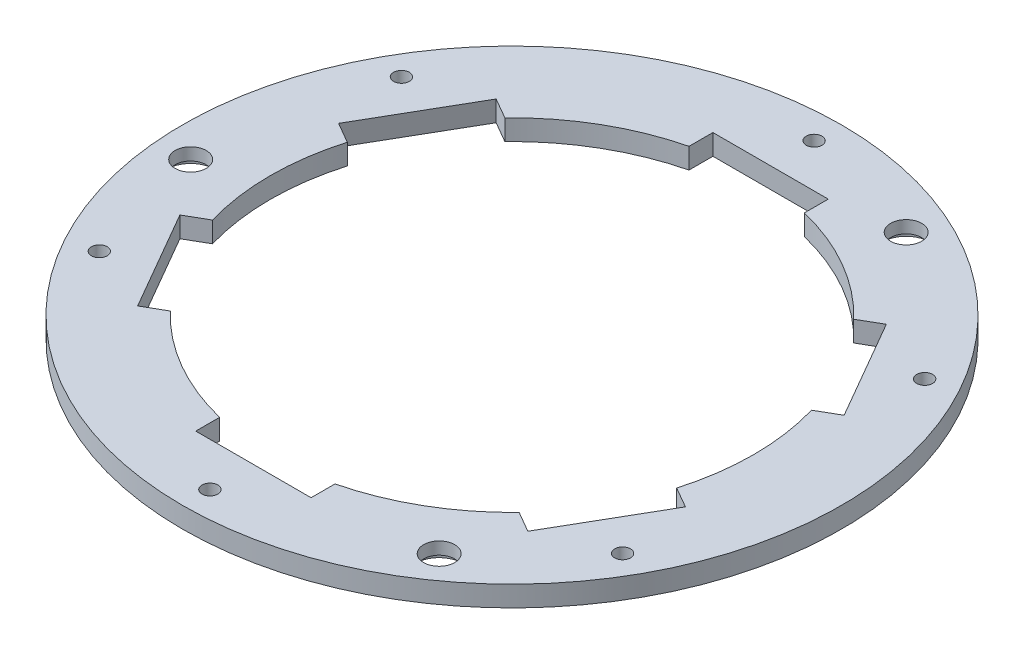
SolidWorks part; units mm, degrees
material "6061 Alloy"
ref_plane "Front Plane" through (0, 0, 0) normal (0, 0, 1) x (1, 0, 0)
ref_plane "Top Plane" through (0, 0, 0) normal (0, 1, 0) x (1, 0, 0)
ref_plane "Right Plane" through (0, 0, 0) normal (1, 0, 0) x (0, 0, -1)
sketch "Sketch1" plane through (0, 0, 0) normal (0, 1, 0) x (1, 0, 0)
  line L0 (-13.335, -54.2656) -> (-13.335, -58.1814)
  line L1 (13.335, -54.2656) -> (13.335, -58.1814)
  line L2 (-13.335, -59.7901) -> (13.335, -59.7901)
  line L3 (13.335, -58.1814) -> (13.335, -59.7901)
  line L4 (-13.335, -58.1814) -> (-13.335, -59.7901)
  line L5 (0, 0) -> (-68.319, -5.9771) construction
  line L6 (0, 0) -> (0, -23.1086) construction
  line L7 (0, 0) -> (17.8146, -65.9496) construction
  line L8 (0, 0) -> (27.4515, -55.5868) construction
  circle A0 centre (0, 0) radius 55.88
  circle A1 centre (0, 0) radius 76.2
  circle A2 centre (0, 0) radius 59.69
  circle A3 centre (0, -69.85) radius 1.8288
  circle A4 centre (-68.319, -5.9771) radius 3.5941
  dimension "D1" = 111.76
  dimension "D2" = 152.4
  dimension "D8" = 3.6576
  dimension "D11" = 7.1882
  dimension "D4" = 13.335
  dimension "D5" = 13.335
  dimension "D7" = 69.85
  dimension "D6" = 5.5245
  dimension "D9" = 68.58
  dimension "D10" = 85
  dimension "D13" = 17.8146
  dimension "D14" = 68.3133
  dimension "D16" = 61.9958
  dimension "D17" = 14.1512
  dimension "D3" = 3.81
extrude "Boss-Extrude1" add sketch "Sketch1" along normal blind 4.7625 contours L1 A2 L0 A0 | A1 A2 A0 region at (-15.0127, 0, 56.2235) region at (-74.0447, 0, 0)
pattern_circular "CirPattern1" count 6 over 360 about axis through (0, 4.7625, 0) along (0, 1, 0) of face at (-13.335, 2.3813, 57.0278) of face at (13.335, 2.3813, 57.0278) of face at (0, 4.7625, 71.6788) of face at (0, 2.3813, 59.7901)
sketch "Sketch2" plane through (0, 0, 0) normal (1, 0, 0) x (0, 0, -1)
  line L0 (76.2, 4.7625) -> (-76.2, 4.7625) construction
  line L1 (-76.2, 0) -> (76.2, 0) construction
  line L2 (76.2, 4.7625) -> (-76.2, 4.7625)
  line L3 (-76.2, 0) -> (76.2, 0)
  line L4 (0, 0) -> (0, 4.7625) construction
  circle A0 centre (-75.2856, 0) radius 2.667
  dimension "D1" = 5.334
  dimension "D2" = 0.9144
revolve "Cut-Revolve1" [suppressed] cut sketch "Sketch2" angle 360 about L4
sketch "Sketch4" plane through (0, 0, 0) normal (0, -1, 0) x (1, 0, 0)
  line L0 (0, 0) -> (-68.319, 5.9771) construction
  line L1 (0, 0) -> (0, -39.7137) construction
  circle A0 centre (-68.319, 5.9771) radius 5.588
  circle A2 centre (-68.319, 5.9771) radius 3.5941 construction
  circle A3 centre (-68.319, 5.9771) radius 3.5941
  dimension "D2" = 11.176
extrude "Cut-Extrude1" cut sketch "Sketch4" against normal blind 1.905 contours A0 region at (-73.749, 0, 5.9771)
pattern_circular "CirPattern2" count 3 over 360 about axis through (0, 0, 0) along (0, 1, 0) of face at (-68.319, 4.7625, 9.5712) of face at (-68.319, 1.905, 2.383) of face at (-68.319, 1.905, 0.3891)
sketch "Sketch5" plane through (0, 4.7625, 0) normal (0, 1, 0) x (1, 0, 0)
  line L0 (0, 0) -> (-20.0894, -55.1952)
  line L1 (0, 0) -> (0, -18.6852)
  line L2 (-16.5968, -53.0258) -> (-18.2257, -57.5011) construction
  line L3 (-18.2257, -57.5011) -> (-22.9993, -55.7636) construction
  line L4 (-22.9993, -55.7636) -> (-21.3704, -51.2884) construction
  line L5 (-59.7924, -7.9638) -> (-55.1022, -7.1368)
  line L6 (-54.2201, -12.1397) -> (-58.9103, -12.9667)
  line L7 (-58.9103, -12.9667) -> (-59.7924, -7.9638)
  line L8 (-36.7931, 47.7998) -> (-33.7318, 44.1515)
  line L9 (-37.6233, 40.8862) -> (-40.6846, 44.5345)
  line L10 (-40.6846, 44.5345) -> (-36.7931, 47.7998)
  line L11 (22.9993, 55.7636) -> (21.3704, 51.2884)
  line L12 (16.5968, 53.0258) -> (18.2257, 57.5011)
  line L13 (18.2257, 57.5011) -> (22.9993, 55.7636)
  line L14 (59.7924, 7.9638) -> (55.1022, 7.1368)
  line L15 (54.2201, 12.1397) -> (58.9103, 12.9667)
  line L16 (58.9103, 12.9667) -> (59.7924, 7.9638)
  line L17 (36.7931, -47.7998) -> (33.7318, -44.1515)
  line L18 (37.6233, -40.8862) -> (40.6846, -44.5345)
  line L19 (40.6846, -44.5345) -> (36.7931, -47.7998)
  circle A0 centre (0, 0) radius 55.5625
  circle A1 centre (0, 0) radius 58.7375 construction
  circle A2 centre (0, 0) radius 55.5625
  circle A3 centre (0, 0) radius 55.5625
  circle A4 centre (0, 0) radius 55.5625
  circle A5 centre (0, 0) radius 55.5625
  circle A6 centre (0, 0) radius 55.5625
  circle A7 centre (0, 0) radius 76.2
  circle A8 centre (0, 0) radius 63.5
  point P38 (0, 0)
  dimension "D1" = 111.125
  dimension "D3" = 20
  dimension "D4" = 2.54
  dimension "D5" = 4.7625
  dimension "D6" = 2.54
  dimension "D2" = 3.175
  dimension "D8" = 12.7
  dimension "D7" = 6
split line "Split Line1" [suppressed]
equation "\"Middle Coupler Inner Daimeter\"= 3.875in"
equation "\"Middle Coupler  Wall Thickness\" = 0.25in"
equation "\"Middle Coupler Bottom Thickness\"= 0.2in"
equation "\"Bearing Rail Offset\"= 0.45in"
equation "\"3-56 UNF Tap\"= 0.089in"
equation "\"3-56 UNF Clearance\"= 0.104in"
equation "\"Ball Bearing Distance\"= 0.03in"
equation "\"D1@Sketch1\"=\"Middle Coupler Inner Daimeter\"+0.5+0.0125*2in"
equation "\"TCA Outer Diameter\" = 6in"
equation "\"D2@Sketch1\"=\"TCA Outer Diameter\""
equation "\"D4@Sketch1\"=0.50 + (0.05/2)"
equation "\"D5@Sketch1\"=\"D4@Sketch1\""
equation "\"D7@Sketch1\"=(\"D2@Sketch1\"-0.5)/2"
equation "\"D8@Sketch1\"=\"6-32 Clearance\""
equation "\"D2@Sketch2\"=\"Interstage Aeroframe Wall Thickness\"/2"
equation "\"Interstage Aeroframe Wall Thickness\" = 0.072in"
equation "\"Compression Spring OD\"= 0.42in"
equation "\"10-24 Tap\"= 0.157in"
equation "\"10-24 Clearance\"= 0.196in"
equation "\"D2@Sketch4\"=\"Compression Spring OD\"+0.02"
equation "\"D3@Sketch1\"=0.125in+(0.05/2)"
equation "\"Lower Stage Fuselage Wall Thickness\" = 0.25in"
equation "\"6-32 Tap\" = 0.107in"
equation "\"1/4-20 Tap\" = 0.201in"
equation "\"3-48 Tap\"= 0.079in"
equation "\"12-24 Tap\" = 0.177in"
equation "\"3-48 Clearance\" = 0.104in"
equation "\"6-32 Clearance\" = 0.144"
equation "\"D6@Sketch1\"=3/16 + 0.03"
equation "\"D9@Sketch1\"=(\"D2@Sketch1\"+\"D1@Sketch1\")/4+0.1"
equation "\"D1@Sketch5\"=\"Middle Coupler Inner Daimeter\"+0.5"
equation "\"D5@Sketch5\"=3/16"
equation "\"D6@Sketch5\"=\"D4@Sketch5\""
equation "\"D1@Boss-Extrude1\"=3/16"
